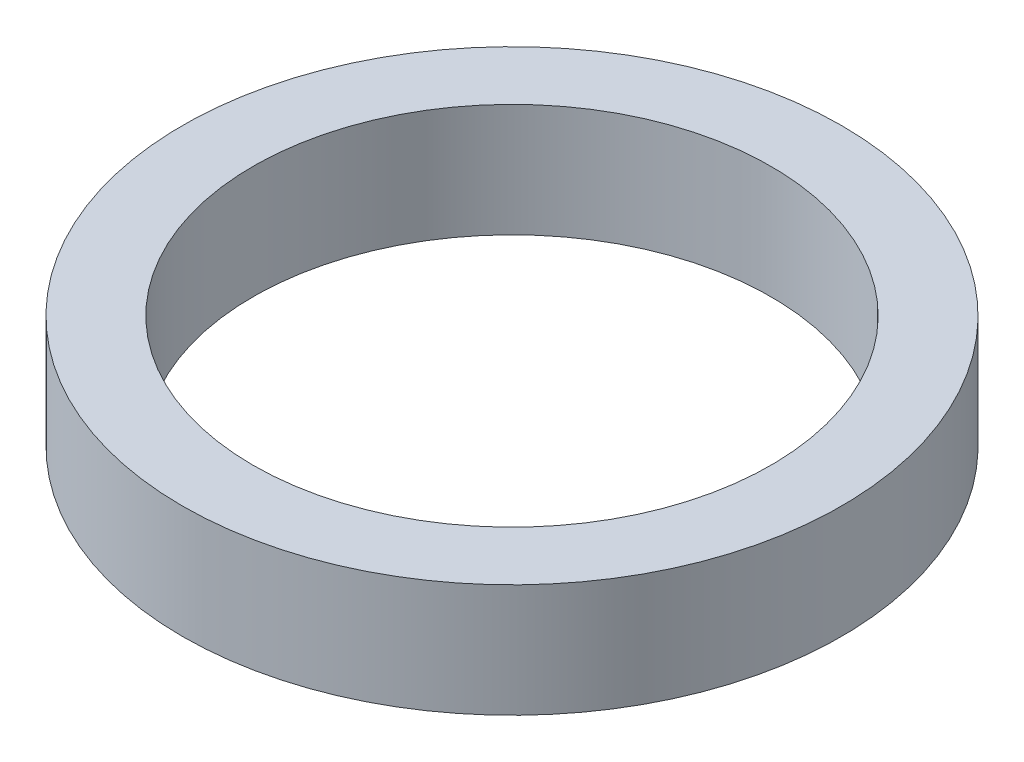
SolidWorks part; units mm, degrees
ref_plane "Front Plane" through (0, 0, 0) normal (0, 0, 1) x (1, 0, 0)
ref_plane "Top Plane" through (0, 0, 0) normal (0, 1, 0) x (1, 0, 0)
ref_plane "Right Plane" through (0, 0, 0) normal (1, 0, 0) x (0, 0, -1)
sketch "Sketch1" plane through (0, 0, 0) normal (0, 1, 0) x (1, 0, 0)
  circle A0 centre (0, 0) radius 35
  dimension "FLANGE_OD" = 70
extrude "Boss-Extrude1" add sketch "Sketch1" along normal blind 12
sketch "Sketch2" plane through (0, 0, 0) normal (0, 1, 0) x (1, 0, 0)
  circle A0 centre (0, 0) radius 27.5
  dimension "BORE_D" = 55
extrude "Cut-Extrude1" cut sketch "Sketch2" along normal through all
sketch "Sketch3" plane through (0, 12, 0) normal (0, 1, 0) x (1, 0, 0)
  circle A0 centre (0, 0) radius 15.8666 construction
  circle A1 centre (-15.8666, 0) radius 1.5
  dimension "BOLT_D" = 3
  dimension "BOLT_PCD" = 31.7332
extrude "Cut-Extrude2" cut sketch "Sketch3" against normal blind 9.222 rebuild error yes
pattern_circular "CirPattern1" count 4 over 360 rebuild error yes
